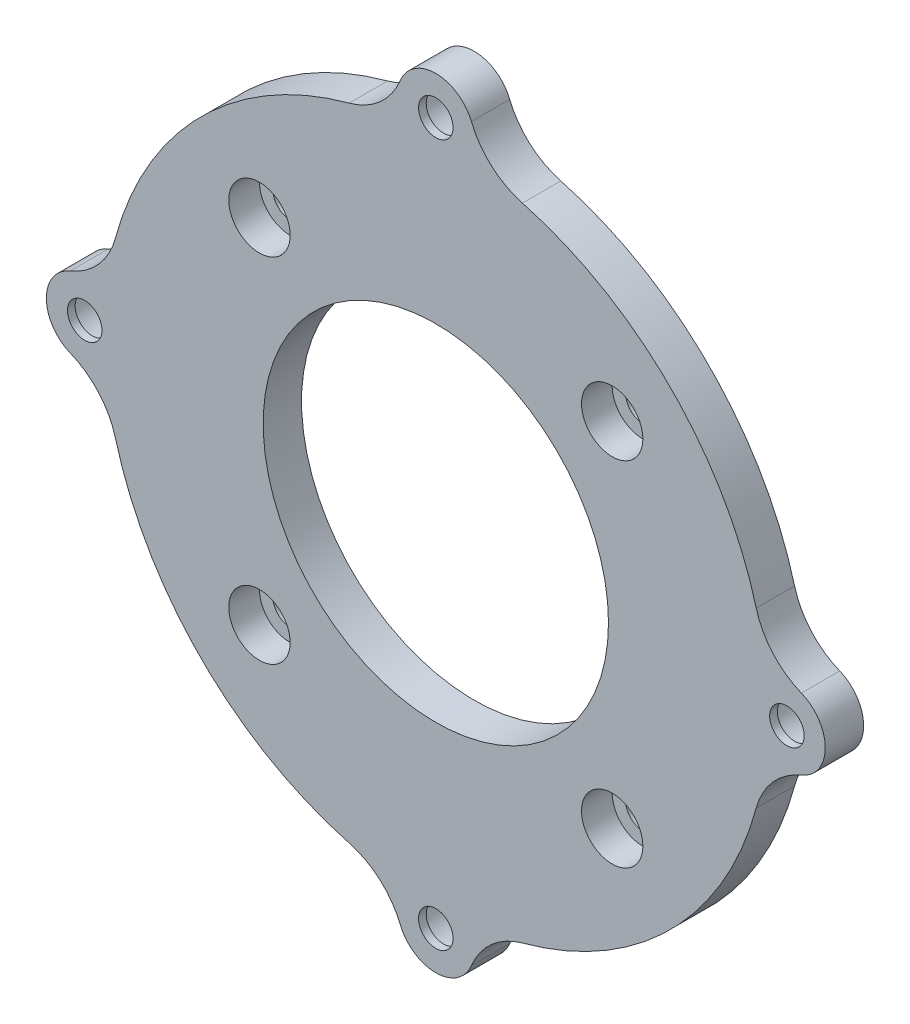
SolidWorks part; units mm, degrees
ref_plane "Front Plane" through (0, 0, 0) normal (0, 0, 1) x (1, 0, 0)
ref_plane "Top Plane" through (0, 0, 0) normal (0, 1, 0) x (1, 0, 0)
ref_plane "Right Plane" through (0, 0, 0) normal (1, 0, 0) x (0, 0, -1)
sketch "Sketch1" plane through (0, 0, 0) normal (0, 0, 1) x (1, 0, 0)
  line L0 (0, 0) -> (-22.981, 22.981) construction
  line L1 (0, 0) -> (-30.5824, 30.5824) construction
  line L2 (-30.5824, 30.5824) -> (30.5824, 30.5824) construction
  line L3 (30.5824, 30.5824) -> (0, 0) construction
  circle A0 centre (0, 0) radius 45.75 construction
  circle A1 centre (0, 0) radius 32.5 construction
  circle A3 centre (-45.75, 0) radius 2.25
  circle A4 centre (0, 0) radius 32.5 construction
  circle A5 centre (0, 45.75) radius 2.25
  circle A6 centre (0, 0) radius 32.5 construction
  circle A7 centre (45.75, 0) radius 2.25
  circle A8 centre (0, 0) radius 32.5 construction
  circle A9 centre (0, -45.75) radius 2.25
  circle A10 centre (-22.981, 22.981) radius 2.25
  circle A11 centre (22.981, 22.981) radius 2.25
  circle A12 centre (22.981, -22.981) radius 2.25
  circle A13 centre (-22.981, -22.981) radius 2.25
  circle A14 centre (0, 0) radius 22.5
  arc A16 (4.631, 47.6352) -> (-4.631, 47.6352) centre (0, 45.75) ccw
  arc A17 (-4.631, 47.6352) -> (-11.2839, 41.7521) centre (-13.8929, 51.4057) cw
  arc A18 (4.631, 47.6352) -> (11.2839, 41.7521) centre (13.8929, 51.4057) ccw
  arc A19 (-41.7521, -11.2839) -> (-11.2839, -41.7521) centre (0, 0) ccw
  arc A20 (47.6352, 4.631) -> (41.7521, 11.2839) centre (51.4057, 13.8929) cw
  arc A21 (47.6352, -4.631) -> (47.6352, 4.631) centre (45.75, 0) ccw
  arc A22 (47.6352, -4.631) -> (41.7521, -11.2839) centre (51.4057, -13.8929) ccw
  arc A23 (4.631, -47.6352) -> (11.2839, -41.7521) centre (13.8929, -51.4057) cw
  arc A24 (-4.631, -47.6352) -> (4.631, -47.6352) centre (0, -45.75) ccw
  arc A25 (-4.631, -47.6352) -> (-11.2839, -41.7521) centre (-13.8929, -51.4057) ccw
  arc A26 (-47.6352, -4.631) -> (-41.7521, -11.2839) centre (-51.4057, -13.8929) cw
  arc A27 (-47.6352, 4.631) -> (-47.6352, -4.631) centre (-45.75, 0) ccw
  arc A28 (-47.6352, 4.631) -> (-41.7521, 11.2839) centre (-51.4057, 13.8929) ccw
  arc A29 (-11.2839, 41.7521) -> (-41.7521, 11.2839) centre (0, 0) ccw
  arc A30 (41.7521, 11.2839) -> (11.2839, 41.7521) centre (0, 0) ccw
  arc A31 (11.2839, -41.7521) -> (41.7521, -11.2839) centre (0, 0) ccw
  point P19 (0, 0)
  point P28 (0, 0)
  point P58 (0, 0)
  dimension "D1" = 4.5
  dimension "D3" = 4.5
  dimension "D5" = 45
  dimension "D6" = 10
  dimension "D7" = 91.5
  dimension "D8" = 65
  dimension "D11" = 10
  dimension "D12" = 10
  dimension "D9" = 0
  dimension "D13" = 90
  dimension "D2" = 4
  dimension "D4" = 4
  dimension "D14" = 4
extrude "Boss-Extrude1" add sketch "Sketch1" along normal mid plane 5
sketch "Sketch3" plane through (0, 0, 2.5) normal (0, 0, 1) x (1, 0, 0)
  circle A3 centre (-22.981, -22.981) radius 4
  circle A6 centre (-22.981, 22.981) radius 4
  circle A9 centre (22.981, 22.981) radius 4
  circle A12 centre (22.981, -22.981) radius 4
  point P15 (0, 0)
  dimension "D1" = 8
extrude "Cut-Extrude2" cut sketch "Sketch3" against normal blind 4
sketch "Sketch4" plane through (0, 0, -2.5) normal (0, 0, -1) x (-1, 0, 0)
  circle A2 centre (0, 45.75) radius 4
  circle A4 centre (45.75, 0) radius 4
  circle A6 centre (0, -45.75) radius 4
  circle A8 centre (-45.75, 0) radius 4
  point P2 (0, 0)
  point P13 (0, 0)
  dimension "D1" = 8
extrude "Cut-Extrude3" cut sketch "Sketch4" against normal blind 4
